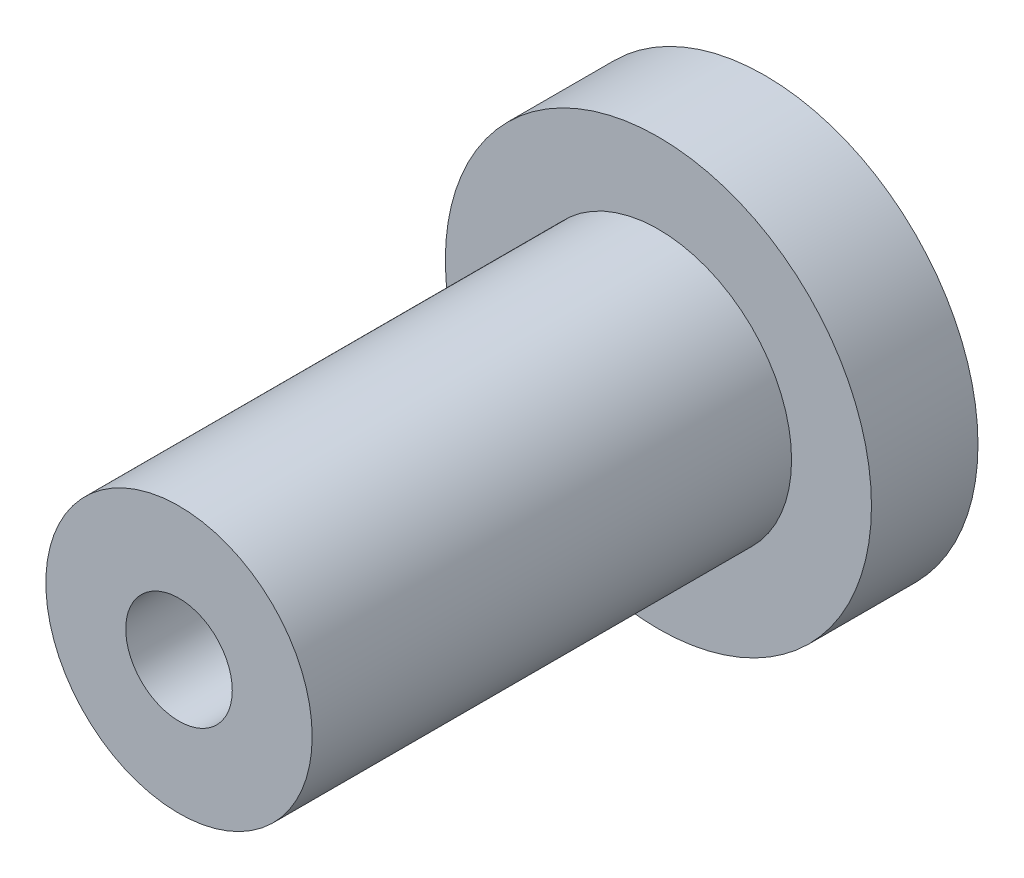
SolidWorks part; units mm, degrees
material "PETG"
ref_plane "Front Plane" through (0, 0, 0) normal (0, 0, 1) x (1, 0, 0)
ref_plane "Top Plane" through (0, 0, 0) normal (0, 1, 0) x (1, 0, 0)
ref_plane "Right Plane" through (0, 0, 0) normal (1, 0, 0) x (0, 0, -1)
sketch "Эскиз1" plane through (0, 0, 0) normal (0, 0, 1) x (1, 0, 0)
  circle A0 centre (0, 0) radius 1
  circle A2 centre (0, 0) radius 2.5
  circle A3 centre (0, 0) radius 4
  dimension "D1" = 2
  dimension "D2" = 5
  dimension "D3" = 8
extrude "Бобышка-Вытянуть1" add sketch "Эскиз1" along normal blind 2 contours A3 A2 | A2 A0 region at (-2.4293, 0, 0) region at (-3.8869, 0, 0)
extrude "Бобышка-Вытянуть2" add sketch "Эскиз1<3>" along normal blind 11 contours A2 A0 region at (-2.4293, 0, 0)
sketch "Эскиз1<3>" plane through (0, 0, 0) normal (0, 0, 1) x (1, 0, 0) same geometry as "Эскиз1"
